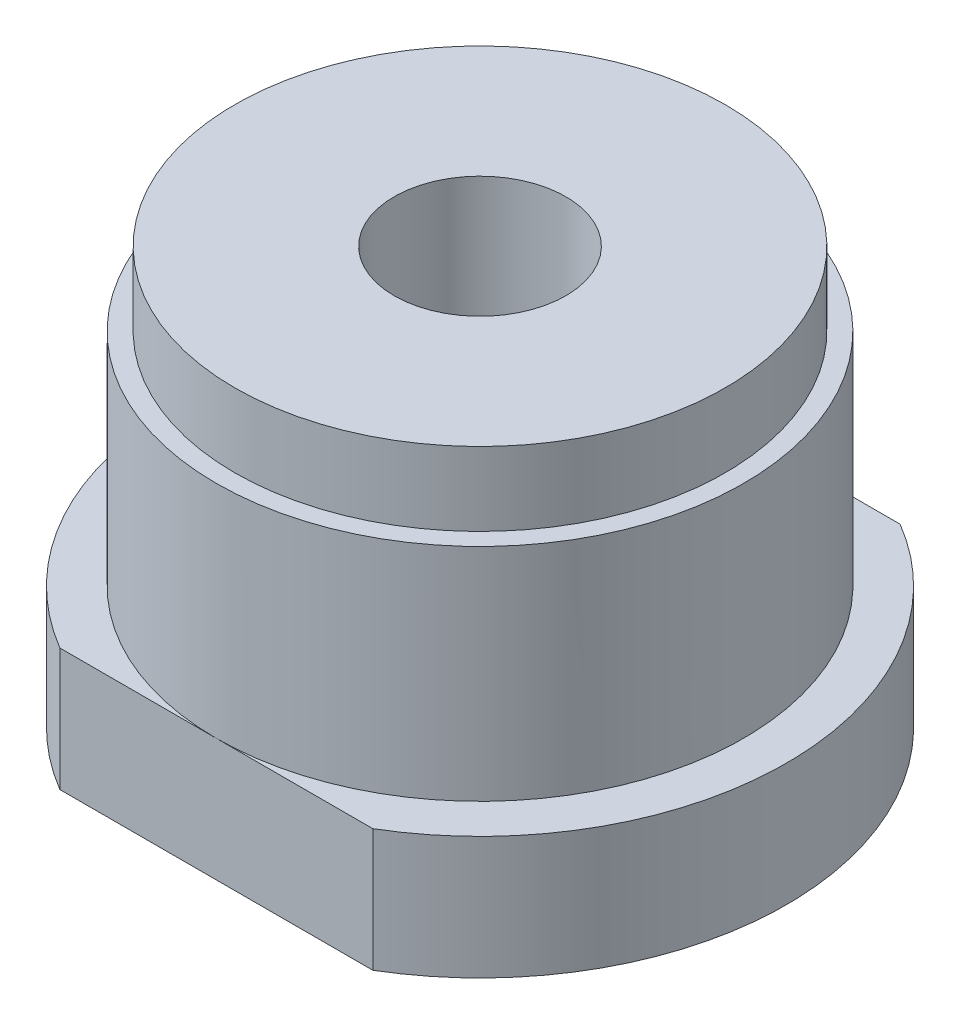
SolidWorks part; units mm, degrees
ref_plane "Front Plane" through (0, 0, 0) normal (0, 0, 1) x (1, 0, 0)
ref_plane "Top Plane" through (0, 0, 0) normal (0, 1, 0) x (1, 0, 0)
ref_plane "Right Plane" through (0, 0, 0) normal (1, 0, 0) x (0, 0, -1)
sketch "Sketch1" plane through (0, 0, 0) normal (0, 1, 0) x (1, 0, 0)
  circle A0 centre (0, 0) radius 12.5
  dimension "D1" = 25
extrude "Boss-Extrude1" add sketch "Sketch1" along normal blind 17
sketch "Sketch2" plane through (0, 17, 0) normal (0, 1, 0) x (1, 0, 0)
  circle A0 centre (0, 0) radius 3.5
  dimension "D1" = 7
extrude "Cut-Extrude1" cut sketch "Sketch2" against normal offset from surface (15 mm away) 2 up to face at (0, 0, 12.5)
sketch "Sketch3" plane through (0, 0, 0) normal (1, 0, 0) x (0, 0, -1)
  line L0 (0, 11) -> (0, -11) construction
  line L1 (13.75, 0) -> (-13.75, 0) construction
  circle A0 centre (8, 3) radius 1.5
  dimension "D1" = 3
  dimension "D2" = 8
  dimension "D3" = 3
extrude "Cut-Extrude2" [suppressed] cut sketch "Sketch3" against normal through all and the other way through all
mirror "Mirror1" [suppressed] about plane through (0, 0, 0) normal (0, 0, 1)
sketch "Sketch4" plane through (0, 17, 0) normal (0, 1, 0) x (1, 0, 0)
  circle A0 centre (0, 0) radius 10
  dimension "D1" = 20
extrude "Cut-Extrude3" cut sketch "Sketch4" against normal offset from surface (12 mm away) 5 flip side to cut up to face at (0, 0, 12.5)
sketch "Sketch5" plane through (0, 0, 0) normal (0, -1, 0) x (1, 0, 0)
  line L0 (9.35, 0) -> (-9.35, 0) construction
  circle A0 centre (-8, 0) radius 1.25
  dimension "D1" = 2.5
  dimension "D2" = 8
extrude "Cut-Extrude4" cut sketch "Sketch5" against normal blind 10
mirror "Mirror2" about plane through (0, 0, 0) normal (1, 0, 0) of "Cut-Extrude4"
sketch "Sketch6" plane through (0, 5, 0) normal (0, 1, 0) x (1, 0, 0)
  line L0 (0, -9.35) -> (0, 9.35) construction
  circle A0 centre (0, 12.5) radius 2.5
  circle A1 centre (0, 0) radius 10 construction
  dimension "D1" = 5
extrude "Cut-Extrude5" [suppressed] cut sketch "Sketch6" against normal blind 5
sketch "Sketch8" plane through (0, 5, 0) normal (0, 1, 0) x (1, 0, 0)
  circle A0 centre (0, 0) radius 10.75
  circle A1 centre (0, 0) radius 4
  dimension "D1" = 21.5
extrude "Boss-Extrude3" add sketch "Sketch8" along normal blind 9
sketch "Sketch7" plane through (0, 5, 0) normal (0, 1, 0) x (1, 0, 0)
  line L1 (-11.0868, 15.6344) -> (11.839, 15.6344)
  line L2 (-11.0868, 15.6344) -> (-11.0868, 10.75)
  line L3 (-11.0868, 10.75) -> (11.839, 10.75)
  line L4 (11.839, 15.6344) -> (11.839, 10.75)
  circle A0 centre (0, 0) radius 10.75 construction
extrude "Cut-Extrude6" cut sketch "Sketch7" against normal through all
mirror "Mirror3" about plane through (0, 0, 0) normal (0, 0, 1) of "Cut-Extrude6"
pattern_circular "CirPattern1" [suppressed] count 12 over 360 of bodies 109
fillet "Fillet1" [suppressed] radius 1
